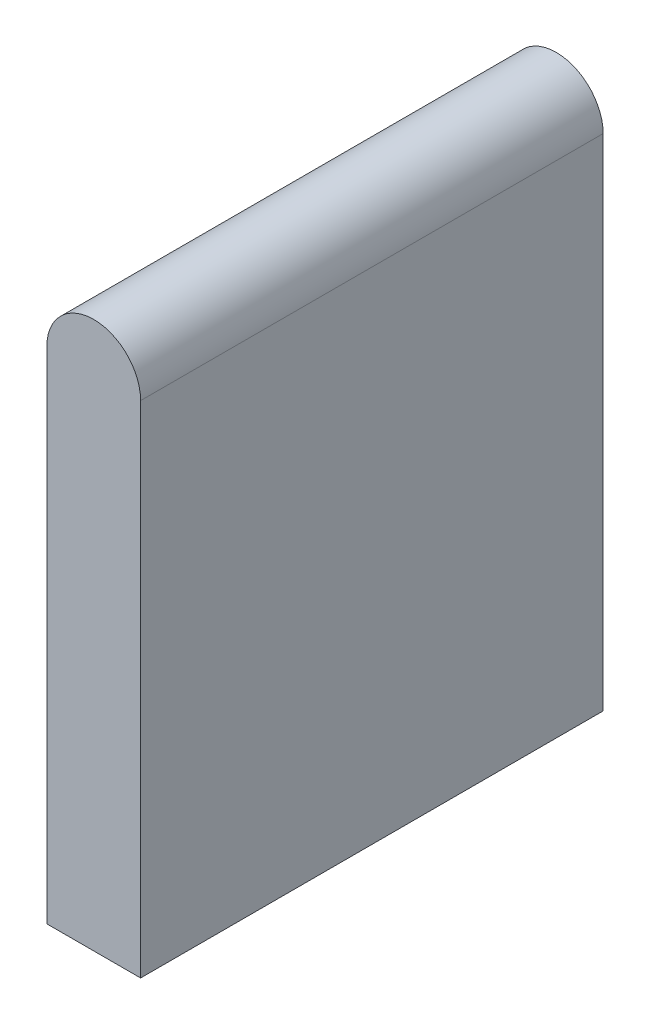
SolidWorks part; units mm, degrees
ref_plane "Front Plane" through (0, 0, 0) normal (0, 0, 1) x (1, 0, 0)
ref_plane "Top Plane" through (0, 0, 0) normal (0, 1, 0) x (1, 0, 0)
ref_plane "Right Plane" through (0, 0, 0) normal (1, 0, 0) x (0, 0, -1)
sketch "Sketch1" plane through (0, 0, 0) normal (0, 0, 1) x (1, 0, 0)
  line L2 (7.5, 0) -> (7.5, -80)
  line L3 (7.5, -80) -> (-7.5, -80)
  line L4 (-7.5, 0) -> (-7.5, -80)
  arc A0 (7.5, 0) -> (-7.5, 0) centre (0, 0) ccw
  dimension "D4" = 15
  dimension "D1" = 15
  dimension "D2" = 7.5
  dimension "D3" = 80
extrude "Boss-Extrude1" add sketch "Sketch1" along normal mid plane 74
